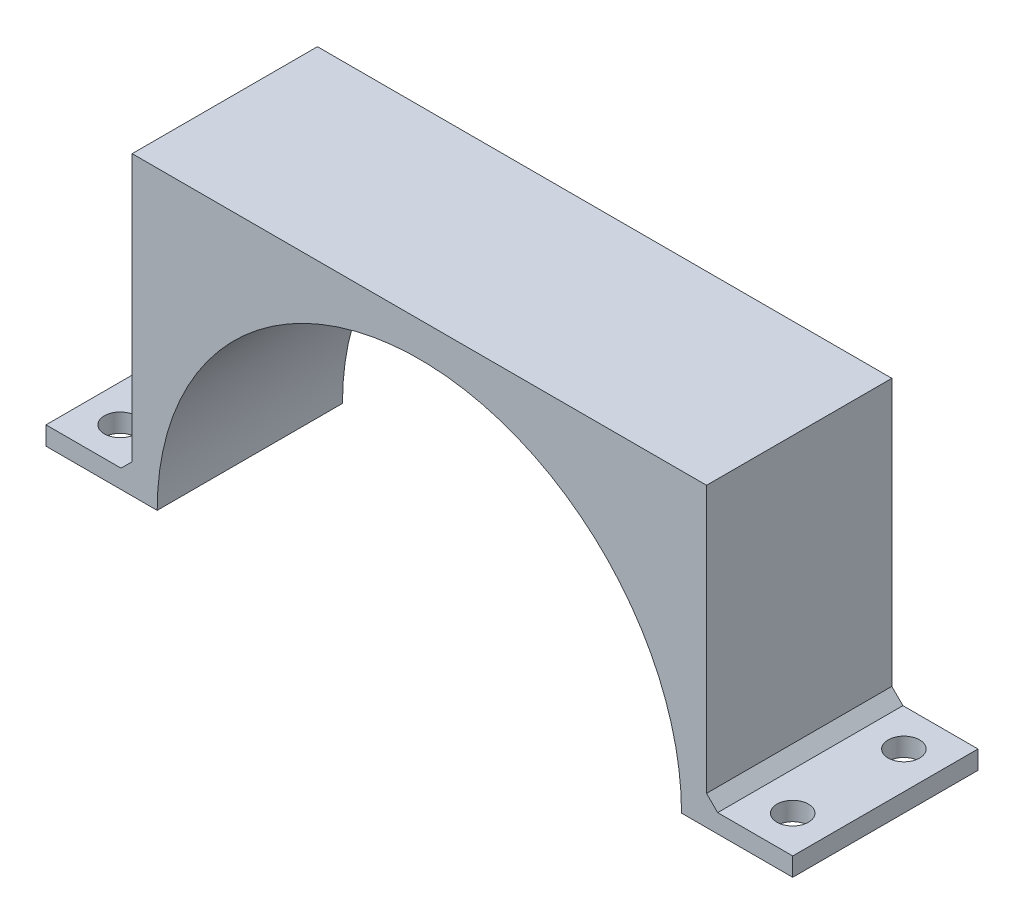
SolidWorks part; units mm, degrees
ref_plane "Płaszczyzna przednia" through (0, 0, 0) normal (0, 0, 1) x (1, 0, 0)
ref_plane "Płaszczyzna górna" through (0, 0, 0) normal (0, 1, 0) x (1, 0, 0)
ref_plane "Płaszczyzna prawa" through (0, 0, 0) normal (1, 0, 0) x (0, 0, -1)
sketch "Szkic1" plane through (0, 0, 0) normal (0, 0, 1) x (1, 0, 0)
  line L0 (70.75, 0) -> (100.75, 0)
  line L1 (100.75, 0) -> (100.75, 5)
  line L2 (100.75, 5) -> (77.5, 5)
  line L3 (77.5, 5) -> (77.5, 80)
  line L4 (77.5, 80) -> (-77.5, 80)
  line L5 (-77.5, 80) -> (-77.5, 5)
  line L6 (-77.5, 5) -> (-100.75, 5)
  line L7 (-100.75, 5) -> (-100.75, 0)
  line L8 (-100.75, 0) -> (-70.75, 0)
  line L9 (0, -15.2195) -> (0, 87.4692) construction
  arc A0 (-70.75, 0) -> (70.75, 0) centre (0, 0) cw
  point P16 (0, 80)
  dimension "D1" = 70.75
  dimension "D2" = 5
  dimension "D3" = 80
  dimension "D4" = 155
  dimension "D5" = 90
  dimension "D6" = 5
  dimension "D7" = 30
  dimension "D8" = 30
extrude "Dodanie-wyciągnięcie1" add sketch "Szkic1" along normal blind 50
ref_plane "Płaszczyzna1" through (0, 5, 0) normal (0, 1, 0) x (1, 0, 0)
sketch "Szkic2" plane through (0, 5, 0) normal (0, 1, 0) x (1, 0, 0)
  line L0 (-77.5, 0) -> (-100.75, 0) construction
  line L1 (-100.75, -50) -> (-100.75, 0) construction
  line L2 (-77.5, -50) -> (-100.75, -50) construction
  circle A0 centre (-90.75, -10) radius 4.25
  circle A1 centre (-90.75, -40) radius 4.25
  dimension "D1" = 10
  dimension "D3" = 10
  dimension "D4" = 10
  dimension "D5" = 8.5
  dimension "D6" = 8.5
  dimension "D2" = 10
extrude "Wytnij-wyciągnięcie1" cut sketch "Szkic2" against normal blind 50
mirror "Lustro1" about plane through (0, 0, 0) normal (1, 0, 0) of "Wytnij-wyciągnięcie1"
fillet "Sfazowanie1" radius 3 1 edges at (77.5, 5, 25) type face fillet profile chamfer first side face at (77.5, 42.5, 25) second side face at (95, 5, 10)
fillet "Sfazowanie2" radius 3 1 edges at (-77.5, 5, 25) type face fillet profile chamfer first side face at (-77.5, 42.5, 25) second side face at (-95, 5, 10)
